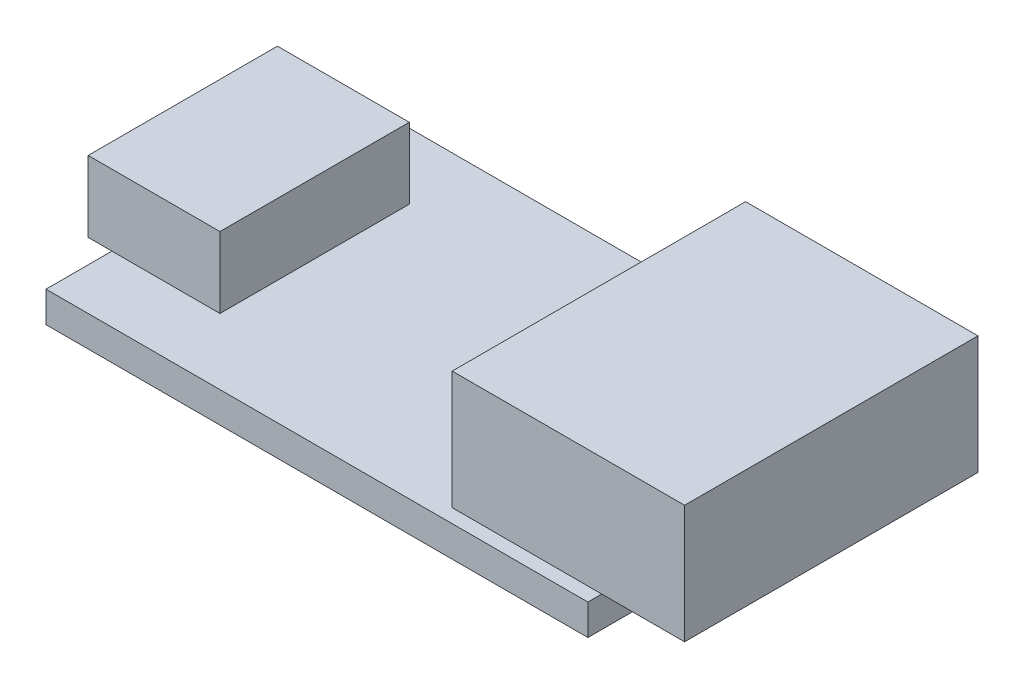
SolidWorks part; units mm, degrees
ref_plane "Front Plane" through (0, 0, 0) normal (0, 0, 1) x (1, 0, 0)
ref_plane "Top Plane" through (0, 0, 0) normal (0, 1, 0) x (1, 0, 0)
ref_plane "Right Plane" through (0, 0, 0) normal (1, 0, 0) x (0, 0, -1)
sketch "Sketch1" plane through (0, 0, 0) normal (0, 1, 0) x (1, 0, 0)
  line L1 (0, 6.785) -> (22.9, 6.785)
  line L2 (0, 6.785) -> (0, -6.785)
  line L3 (0, -6.785) -> (22.9, -6.785)
  line L4 (22.9, 6.785) -> (22.9, -6.785)
  line L5 (0, -55) -> (0, 55) construction
  line L6 (4.5666, 0) -> (0, 0) construction
  line L7 (26.4, 6.2) -> (16.58, 6.2)
  line L8 (26.4, 6.2) -> (26.4, -6.2)
  line L9 (26.4, -6.2) -> (16.58, -6.2)
  line L10 (16.58, 6.2) -> (16.58, -6.2)
  line L11 (-1.0034, 4) -> (4.5666, 4)
  line L12 (-1.0034, 4) -> (-1.0034, -4)
  line L13 (-1.0034, -4) -> (4.5666, -4)
  line L14 (4.5666, 4) -> (4.5666, -4)
  line L15 (22.9, 0) -> (16.58, 0) construction
  line L16 (-55, 0) -> (55, 0) construction
  dimension "D1" = 22.9
  dimension "D2" = 13.57
  dimension "D3" = 9.82
  dimension "D4" = 12.4
  dimension "D5" = 5.57
  dimension "D6" = 8
  dimension "D7" = 3.5
extrude "Boss-Extrude1" add sketch "Sketch1" against normal blind 1.3 contours L1 L4 L3 L2
extrude "Boss-Extrude2" add sketch "Sketch1<3>" along normal blind 5 separate body contours L10 L9 L8 L7
sketch "Sketch1<3>" plane through (0, 0, 0) normal (0, 1, 0) x (1, 0, 0) same geometry as "Sketch1"
extrude "Boss-Extrude3" add sketch "Sketch1<4>" along normal blind 3 separate body contours L13 L14 L11 L12
sketch "Sketch1<4>" plane through (0, 0, 0) normal (0, 1, 0) x (1, 0, 0) same geometry as "Sketch1"
